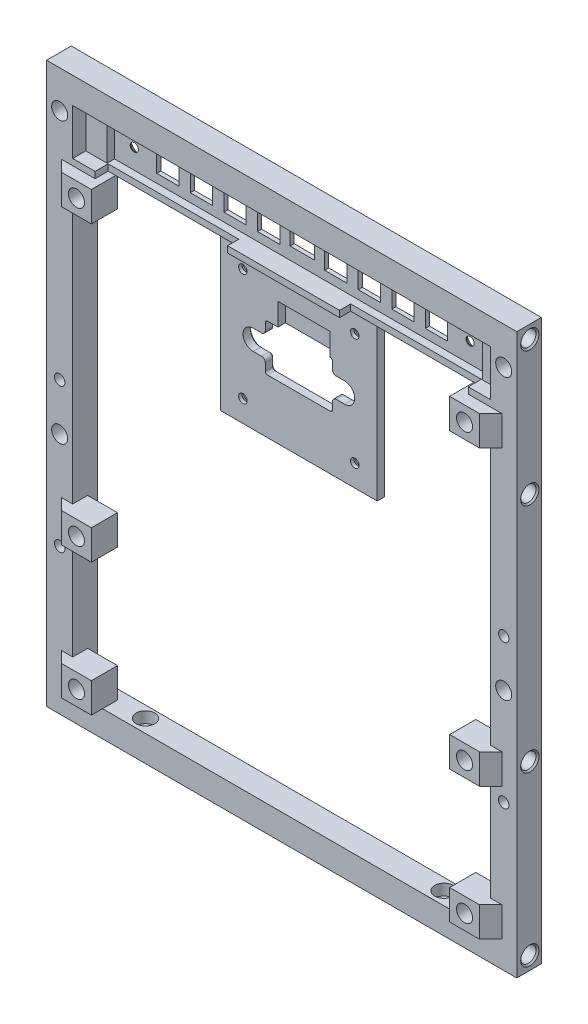
SolidWorks part; units mm, degrees
ref_plane "Front Plane" through (0, 0, 0) normal (0, 0, 1) x (1, 0, 0)
ref_plane "Top Plane" through (0, 0, 0) normal (0, 1, 0) x (1, 0, 0)
ref_plane "Right Plane" through (0, 0, 0) normal (1, 0, 0) x (0, 0, -1)
sketch "Sketch1" plane through (0, 0, 0) normal (0, 0, 1) x (1, 0, 0)
  line L1 (-63, -75) -> (63, -75)
  line L2 (-63, -75) -> (-63, 75)
  line L3 (-63, 75) -> (63, 75)
  line L4 (63, -75) -> (63, 75)
  line L5 (-63, -75) -> (63, 75) construction
  line L6 (-63, 75) -> (63, -75) construction
  line L7 (-56, -68) -> (56, -68)
  line L8 (-56, -68) -> (-56, 68)
  line L9 (-56, 68) -> (56, 68)
  line L10 (56, -68) -> (56, 68)
  line L11 (-56, -68) -> (56, 68) construction
  line L12 (-56, 68) -> (56, -68) construction
  point P0 (0, 0)
  point P6 (0, 0)
  dimension "D1" = 126
  dimension "D2" = 150
  dimension "D3" = 7
  dimension "D4" = 7
extrude "Boss-Extrude1" add sketch "Sketch1" along normal blind 7
sketch "Sketch2" plane through (-63, 0, 0) normal (-1, 0, 0) x (0, 0, 1)
  line L0 (3.5, 71.5) -> (3.5, -71.5) construction
  line L1 (7, 75) -> (0, 75) construction
  circle A0 centre (3.5, -71.5) radius 2.05
  circle A2 centre (3.5, 71.5) radius 2.05
  circle A3 centre (3.5, 35.5) radius 2.05
  circle A4 centre (3.5, -26.5) radius 2.05
  point P2 (3.5, 0)
  point P7 (3.5, 75)
  dimension "D2" = 4.1
  dimension "D3" = 36
  dimension "D4" = 45
  dimension "D1" = 3.5
extrude "Cut-Extrude1" cut sketch "Sketch2" against normal blind 6
mirror "Mirror1" about plane through (0, 0, 0) normal (1, 0, 0) of "Cut-Extrude1"
sketch "Sketch3" plane through (0, -68, 0) normal (0, 1, 0) x (1, 0, 0)
  line L0 (0, 0) -> (0, -7) construction
  line L1 (-56, 0) -> (56, 0) construction
  line L2 (-56, -7) -> (56, -7) construction
  line L3 (40, -3.5) -> (-40, -3.5) construction
  circle A0 centre (40, -3.5) radius 1.35
  circle A1 centre (-40, -3.5) radius 1.35
  point P9 (0, -3.5)
  dimension "D1" = 2.7
  dimension "D2" = 80
extrude "Cut-Extrude2" cut sketch "Sketch3" against normal through all
sketch "Sketch4" plane through (0, -68, 0) normal (0, 1, 0) x (1, 0, 0)
  circle A0 centre (40, -3.5) radius 2.5
  circle A1 centre (-40, -3.5) radius 2.5
  dimension "D1" = 5
extrude "Cut-Extrude3" cut sketch "Sketch4" against normal blind 3
sketch "Sketch5" plane through (0, 0, 0) normal (0, 0, -1) x (-1, 0, 0)
  line L0 (-59.5, -75) -> (-59.5, 75) construction
  line L1 (63, -75) -> (-63, -75) construction
  line L2 (-63, 75) -> (63, 75) construction
  line L3 (-56, 0) -> (-63, 0) construction
  line L4 (-56, -68) -> (-56, 68) construction
  line L5 (-63, -75) -> (-63, 75) construction
  line L6 (0, 75) -> (0, -75) construction
  line L7 (56, -68) -> (-56, -68) construction
  circle A0 centre (-59.5, 2.6) radius 1.4
  circle A1 centre (59.5, 2.6) radius 1.4
  circle A2 centre (-59.5, -36) radius 1.4
  circle A3 centre (59.5, -36) radius 1.4
  point P12 (-59.5, 0)
  point P13 (-59.5, 0)
  dimension "D1" = 2.8
  dimension "D2" = 2.6
  dimension "D3" = 32
extrude "Cut-Extrude4" cut sketch "Sketch5" against normal through all
sketch "Sketch6" plane through (0, 0, 0) normal (0, 0, -1) x (-1, 0, 0)
  circle A0 centre (-59.5, 2.6) radius 2.5
  circle A1 centre (59.5, 2.6) radius 2.5
  circle A2 centre (-59.5, -36) radius 2.5
  circle A3 centre (59.5, -36) radius 2.5
  dimension "D1" = 5
extrude "Cut-Extrude5" cut sketch "Sketch6" against normal blind 3
sketch "Sketch7" plane through (0, 0, 0) normal (0, 0, -1) x (-1, 0, 0)
  line L0 (-56, 68) -> (-63, 68) construction
  line L1 (-63, -75) -> (-63, 75) construction
  line L2 (-59.5, 65) -> (-59.5, -10) construction
  line L3 (-63, 75) -> (63, 75) construction
  circle A0 centre (-59.5, 65) radius 2.15
  circle A1 centre (-59.5, -10) radius 2.15
  point P8 (-59.5, 68)
  dimension "D1" = 4.3
  dimension "D2" = 10
  dimension "D3" = 75
extrude "Cut-Extrude6" cut sketch "Sketch7" against normal through all
mirror "Mirror2" about plane through (0, 0, 0) normal (1, 0, 0) of "Cut-Extrude6"
sketch "Sketch8" plane through (0, 0, 3) normal (0, 0, -1) x (-1, 0, 0)
  line L2 (-60.9, 0.5288) -> (-60.9, 4.6712)
  line L4 (-58.1, 0.5288) -> (-58.1, 4.6712)
  line L5 (-60.9, 0.5288) -> (-58.1, 4.6712) construction
  line L6 (-60.9, 4.6712) -> (-58.1, 0.5288) construction
  line L8 (-60.9, -38.0712) -> (-60.9, -33.9288)
  line L10 (-58.1, -38.0712) -> (-58.1, -33.9288)
  line L11 (-60.9, -38.0712) -> (-58.1, -33.9288) construction
  line L12 (-60.9, -33.9288) -> (-58.1, -38.0712) construction
  circle A0 centre (-59.5, 2.6) radius 2.5 construction
  circle A1 centre (-59.5, -36) radius 2.5 construction
  circle A2 centre (-59.5, -36) radius 2.5 construction
  arc A3 (-58.1, 4.6712) -> (-60.9, 4.6712) centre (-59.5, 2.6) ccw
  arc A4 (-58.1, -33.9288) -> (-60.9, -33.9288) centre (-59.5, -36) ccw
  circle A5 centre (-59.5, 2.6) radius 1.4 construction
  circle A6 centre (-59.5, -36) radius 1.4 construction
  arc A7 (-60.9, -38.0712) -> (-58.1, -38.0712) centre (-59.5, -36) ccw
  arc A8 (-60.9, 0.5288) -> (-58.1, 0.5288) centre (-59.5, 2.6) ccw
  point P0 (-59.5, 2.6)
  point P8 (-59.5, -36)
extrude "Cut-Extrude7" cut sketch "Sketch8" against normal blind 0.2
sketch "Sketch9" plane through (0, 0, 3.2) normal (0, 0, -1) x (-1, 0, 0)
  line L0 (-58.1, 2.6) -> (-58.1, 4.6712) construction
  line L1 (-60.9, 1.2) -> (-58.1, 1.2)
  line L2 (-60.9, 1.2) -> (-60.9, 4)
  line L3 (-60.9, 4) -> (-58.1, 4)
  line L4 (-58.1, 1.2) -> (-58.1, 4)
  line L5 (-60.9, 1.2) -> (-58.1, 4) construction
  line L6 (-60.9, 4) -> (-58.1, 1.2) construction
  line L7 (-58.1, -38.0712) -> (-58.1, -33.9288) construction
  line L8 (-60.9, -37.4) -> (-58.1, -37.4)
  line L9 (-60.9, -37.4) -> (-60.9, -34.6)
  line L10 (-60.9, -34.6) -> (-58.1, -34.6)
  line L11 (-58.1, -37.4) -> (-58.1, -34.6)
  line L12 (-60.9, -37.4) -> (-58.1, -34.6) construction
  line L13 (-60.9, -34.6) -> (-58.1, -37.4) construction
  arc A0 (-58.1, 2.6) -> (-60.9, 2.6) centre (-59.5, 2.6) ccw construction
  point P0 (-59.5, 2.6)
  point P8 (-59.5, -36)
extrude "Cut-Extrude8" cut sketch "Sketch9" against normal blind 0.2
mirror "Mirror3" about plane through (0, 0, 0) normal (1, 0, 0) of "Cut-Extrude8", "Cut-Extrude7"
sketch "Sketch10" plane through (0, 0, 7) normal (0, 0, 1) x (1, 0, 0)
  line L0 (56, -68) -> (56, 68) construction
  line L1 (56, -68) -> (50, -68)
  line L2 (56, -68) -> (56, -62)
  line L3 (56, -62) -> (50, -62)
  line L4 (50, -68) -> (50, -62)
  line L5 (56, -38.5) -> (50, -38.5)
  line L6 (56, -38.5) -> (56, -32.5)
  line L7 (56, -32.5) -> (50, -32.5)
  line L8 (50, -38.5) -> (50, -32.5)
  line L9 (-56, -68) -> (56, -68) construction
  dimension "D1" = 6
  dimension "D2" = 35.5
extrude "Boss-Extrude2" add sketch "Sketch10" against normal offset from surface (5.5 mm away) 1.5 up to face at (-57.35, -10, 0)
sketch "Sketch11" plane through (0, 0, 1.5) normal (0, 0, -1) x (-1, 0, 0)
  line L0 (-56, -38.5) -> (-50, -32.5) construction
  line L2 (-56, -68) -> (-50, -62) construction
  circle A0 centre (-53, -35.5) radius 1.65
  circle A1 centre (-53, -65) radius 1.65
  dimension "D1" = 3.3
extrude "Cut-Extrude9" cut sketch "Sketch11" against normal through all
mirror "Mirror4" about plane through (0, 0, 0) normal (1, 0, 0) of "Cut-Extrude9", "Boss-Extrude2"
sketch "Sketch12" plane through (0, 0, 0) normal (0, 0, -1) x (-1, 0, 0)
  line L0 (56, 68) -> (56, -68) construction
  line L1 (-56, 68) -> (56, 68)
  line L2 (-56, 68) -> (-56, 54)
  line L3 (-56, 54) -> (56, 54)
  line L4 (56, 68) -> (56, 54)
  dimension "D1" = 14
extrude "Boss-Extrude3" add sketch "Sketch12" against normal blind 1.5
sketch "Sketch13" plane through (0, 0, 1.5) normal (0, 0, 1) x (1, 0, 0)
  line L0 (-56, 68) -> (56, 54) construction
  line L2 (-50.3, 55.7) -> (50.3, 55.7)
  line L3 (-50.3, 55.7) -> (-50.3, 66.3)
  line L4 (-50.3, 66.3) -> (50.3, 66.3)
  line L5 (50.3, 55.7) -> (50.3, 66.3)
  line L6 (-50.3, 55.7) -> (50.3, 66.3) construction
  line L7 (-50.3, 66.3) -> (50.3, 55.7) construction
  line L8 (-56, 54) -> (56, 54)
  line L9 (-56, 54) -> (-56, 68)
  line L10 (-56, 68) -> (56, 68)
  line L11 (56, 54) -> (56, 68)
  line L12 (-56, 54) -> (56, 68) construction
  line L13 (-56, 68) -> (56, 54) construction
  point P4 (0, 61)
  point P9 (0, 61)
  dimension "D1" = 100.6
  dimension "D2" = 10.6
extrude "Boss-Extrude4" add sketch "Sketch13" along normal blind 2
sketch "Sketch14" plane through (0, 0, 1.5) normal (0, 0, 1) x (1, 0, 0)
  line L0 (0, 66.3) -> (0, 55.7) construction
  line L1 (50.3, 66.3) -> (-50.3, 66.3) construction
  line L2 (-50.3, 55.7) -> (50.3, 55.7) construction
  line L3 (-50.3, 61) -> (50.3, 61) construction
  line L4 (50.3, 55.7) -> (50.3, 66.3) construction
  line L5 (-33, 64) -> (-39, 64)
  line L6 (-3.25, 59) -> (3.25, 59)
  line L7 (-3.25, 59) -> (-3.25, 63)
  line L8 (-3.25, 63) -> (3.25, 63)
  line L9 (3.25, 59) -> (3.25, 63)
  line L10 (-3.25, 59) -> (3.25, 63) construction
  line L11 (-3.25, 63) -> (3.25, 59) construction
  line L12 (6, 58) -> (12, 58)
  line L13 (6, 58) -> (6, 64)
  line L14 (6, 64) -> (12, 64)
  line L15 (12, 58) -> (12, 64)
  line L16 (6, 58) -> (12, 64) construction
  line L17 (6, 64) -> (12, 58) construction
  line L18 (15, 58) -> (21, 58)
  line L19 (15, 58) -> (15, 64)
  line L20 (15, 64) -> (21, 64)
  line L21 (21, 58) -> (21, 64)
  line L22 (15, 58) -> (21, 64) construction
  line L23 (15, 64) -> (21, 58) construction
  line L24 (24, 58) -> (30, 58)
  line L25 (24, 58) -> (24, 64)
  line L26 (24, 64) -> (30, 64)
  line L27 (30, 58) -> (30, 64)
  line L28 (24, 58) -> (30, 64) construction
  line L29 (24, 64) -> (30, 58) construction
  line L30 (33, 58) -> (39, 58)
  line L31 (33, 58) -> (33, 64)
  line L32 (33, 64) -> (39, 64)
  line L33 (39, 58) -> (39, 64)
  line L34 (33, 58) -> (39, 64) construction
  line L35 (33, 64) -> (39, 58) construction
  line L36 (-39, 58) -> (-39, 64)
  line L37 (-33, 58) -> (-39, 58)
  line L38 (-33, 58) -> (-33, 64)
  line L39 (-24, 64) -> (-30, 64)
  line L40 (-30, 58) -> (-30, 64)
  line L41 (-24, 58) -> (-30, 58)
  line L42 (-24, 58) -> (-24, 64)
  line L43 (-15, 64) -> (-21, 64)
  line L44 (-21, 58) -> (-21, 64)
  line L45 (-15, 58) -> (-21, 58)
  line L46 (-15, 58) -> (-15, 64)
  line L47 (-6, 64) -> (-12, 64)
  line L48 (-12, 58) -> (-12, 64)
  line L49 (-6, 58) -> (-12, 58)
  line L50 (-6, 58) -> (-6, 64)
  circle A0 centre (-45, 61) radius 1.3 construction
  circle A1 centre (45, 61) radius 1.3 construction
  point P6 (0, 61)
  point P11 (0, 61)
  point P16 (9, 61)
  point P21 (18, 61)
  point P26 (27, 61)
  point P31 (36, 61)
  dimension "D10" = 2.6
  dimension "D9" = 45
  dimension "D1" = 6.5
  dimension "D2" = 4
  dimension "D3" = 6
  dimension "D4" = 9
  dimension "D5" = 9
  dimension "D6" = 9
  dimension "D7" = 9
  dimension "D8" = 45
extrude "Cut-Extrude10" cut sketch "Sketch14" against normal through all
sketch "Sketch15" plane through (0, 0, 1.5) normal (0, 0, 1) x (1, 0, 0)
  circle A0 centre (-45, 61) radius 1
  circle A1 centre (45, 61) radius 1
  dimension "D1" = 2
extrude "Boss-Extrude5" add sketch "Sketch15" along normal up to surface (2 mm away) up to face at (0, 61, 3.5)
chamfer "Chamfer1" distance 0.4 angle 45 3 edges at (-56, -7, 0) (56, -7, 0) (0, -68, 0) tangent propagation no
chamfer "Chamfer2" distance 0.4 angle 45 4 edges at (0, 75, 0) (-63, 0, 0) (0, -75, 0) (63, 0, 0)
chamfer "Chamfer3" distance 0.4 angle 45 36 edges at (-36, 58, 0) (-39, 61, 0) (-36, 64, 0) (-33, 61, 0) (-27, 58, 0) (-30, 61, 0) (-27, 64, 0) (-24, 61, 0) (-18, 58, 0) (-21, 61, 0) (-18, 64, 0) (-15, 61, 0) (-9, 58, 0) (-12, 61, 0) (-9, 64, 0) (-6, 61, 0) (0, 59, 0) (-3.25, 61, 0) (0, 63, 0) (3.25, 61, 0) (9, 58, 0) (6, 61, 0) (9, 64, 0) (12, 61, 0) (18, 58, 0) (15, 61, 0) (18, 64, 0) (21, 61, 0) (36, 58, 0) (33, 61, 0) (36, 64, 0) (39, 61, 0) (27, 58, 0) (24, 61, 0) (27, 64, 0) (30, 61, 0)
sketch "Sketch16" plane through (0, 0, 7) normal (0, 0, 1) x (1, 0, 0)
  line L0 (-50, 54) -> (-50, 55.7)
  line L1 (-56, -32.5) -> (-50, -32.5)
  line L2 (-56, -32.5) -> (-56, -26.5)
  line L3 (-56, -26.5) -> (-50, -26.5)
  line L4 (-50, -32.5) -> (-50, -26.5)
  line L5 (56, -32.5) -> (50, -32.5)
  line L6 (56, -32.5) -> (56, -26.5)
  line L7 (56, -26.5) -> (50, -26.5)
  line L8 (50, -32.5) -> (50, -26.5)
  line L9 (56, 54) -> (50, 54) construction
  line L10 (56, 54) -> (56, 48)
  line L11 (56, 48) -> (50, 48)
  line L12 (50, 54) -> (50, 48)
  line L13 (-56, 54) -> (-50, 54) construction
  line L14 (-56, 54) -> (-56, 48)
  line L15 (-56, 48) -> (-50, 48)
  line L16 (-50, 54) -> (-50, 48)
  line L17 (-50.3, 55.7) -> (50.3, 55.7) construction
  line L18 (-50, 55.7) -> (-56, 55.7)
  line L19 (-56, 68) -> (-56, 54) construction
  line L20 (-56, 55.7) -> (-56, 54)
  line L21 (50, 54) -> (50, 55.7)
  line L22 (50, 55.7) -> (56, 55.7)
  line L23 (56, 54) -> (56, 68) construction
  line L24 (56, 55.7) -> (56, 54)
  dimension "D1" = 6
extrude "Boss-Extrude7" add sketch "Sketch16" against normal offset from surface (5.5 mm away) 1.5 up to face at (-36, 61, 0)
sketch "Sketch17" plane through (0, 0, 1.5) normal (0, 0, -1) x (-1, 0, 0)
  line L0 (-50, 48) -> (50, -26.5) construction
  line L1 (-50, -26.5) -> (-50, -38.5) construction
  line L2 (-53, -29.5) -> (53, -29.5) construction
  line L3 (-53, -29.5) -> (-53, 51) construction
  line L4 (-53, 51) -> (53, 51) construction
  line L5 (53, -29.5) -> (53, 51) construction
  line L6 (-53, -29.5) -> (53, 51) construction
  line L7 (-53, 51) -> (53, -29.5) construction
  line L8 (50, -26.5) -> (56, -26.5) construction
  circle A0 centre (-53, -29.5) radius 1.65
  circle A1 centre (53, -29.5) radius 1.65
  circle A2 centre (53, 51) radius 1.65
  circle A3 centre (-53, 51) radius 1.65
  point P4 (0, 10.75)
  dimension "D3" = 3.3
  dimension "D1" = 3
  dimension "D2" = 3
extrude "Cut-Extrude11" cut sketch "Sketch17" against normal through all
sketch "Sketch18" plane through (0, 0, 1.5) normal (0, 0, 1) x (1, 0, 0)
  circle A0 centre (-45, 61) radius 1.1
  circle A1 centre (45, 61) radius 1.1
  dimension "D1" = 2.2
extrude "Cut-Extrude12" cut sketch "Sketch18" against normal through all both and the other way through all
chamfer "Chamfer4" distance 1.3 angle 45 2 edges at (-43.9, 61, 0) (46.1, 61, 0)
sketch "Sketch19" plane through (0, 0, 1.5) normal (0, 0, -1) x (-1, 0, 0)
  line L1 (-56, -68) -> (56, -68)
  line L2 (-56, -68) -> (-56, 54)
  line L3 (-56, 54) -> (56, 54)
  line L4 (56, -68) -> (56, 54)
extrude "Cut-Extrude13" cut sketch "Sketch19" against normal through all
ref_plane "Plane1" through (0, 0, 3) normal (0, 0, 1) x (1, 0, 0)
sketch "Sketch20" plane through (0, 0, 3) normal (0, 0, 1) x (1, 0, 0)
  line L0 (56, 54) -> (56, -68) construction
  line L1 (56, -68) -> (48, -68)
  line L2 (56, -68) -> (56, -60)
  line L3 (56, -60) -> (48, -60)
  line L4 (48, -68) -> (48, -60)
  line L5 (56, 54) -> (48, 54)
  line L6 (56, 54) -> (56, 46)
  line L7 (56, 46) -> (48, 46)
  line L8 (48, 54) -> (48, 46)
  line L9 (56, -24.5) -> (48, -24.5)
  line L10 (56, -24.5) -> (56, -32.5)
  line L11 (56, -32.5) -> (48, -32.5)
  line L12 (48, -24.5) -> (48, -32.5)
  dimension "D1" = 8
  dimension "D2" = 27.5
extrude "Boss-Extrude8" add sketch "Sketch20" along normal blind 7
sketch "Sketch21" plane through (0, 0, 3) normal (0, 0, -1) x (-1, 0, 0)
  line L0 (-48, 54) -> (-56, 46) construction
  line L1 (-56, -60) -> (-48, -68) construction
  line L2 (-56, -24.5) -> (-48, -32.5) construction
  circle A0 centre (-52, 50) radius 2.15
  circle A1 centre (-52, -64) radius 2.15
  circle A2 centre (-52, -28.5) radius 2.15
  dimension "D1" = 4.3
extrude "Cut-Extrude14" cut sketch "Sketch21" against normal through all
mirror "Mirror5" about plane through (0, 0, 0) normal (1, 0, 0) of "Cut-Extrude14", "Boss-Extrude8"
chamfer "Chamfer5" distance 3 angle 45 6 edges at (-56, -64, 7) (56, -64, 7) (56, 50, 7) (-56, 50, 7) (-56, -28.5, 7) (56, -28.5, 7)
sketch "Sketch23" plane through (0, 0, 0) normal (0, 0, -1) x (-1, 0, 0)
  line L0 (-56.4, 54) -> (56.4, 54) construction
  line L1 (-15, 54) -> (15, 54)
  line L2 (-15, 54) -> (-15, 29)
  line L3 (-15, 29) -> (15, 29)
  line L4 (15, 54) -> (15, 29)
  point P6 (0, 29)
  dimension "D1" = 25
  dimension "D2" = 30
extrude "Boss-Extrude10" add sketch "Sketch23" against normal up to surface (3.5 mm away) up to face at (0, 54.5667, 3.5)
sketch "Sketch24" plane through (0, 0, 3.5) normal (0, 0, 1) x (1, 0, 0)
  line L0 (15, 29) -> (-15, 29) construction
  line L1 (-12.7, 29) -> (12.7, 29)
  line L2 (-12.7, 29) -> (-12.7, 54)
  line L3 (-12.7, 54) -> (12.7, 54)
  line L4 (12.7, 29) -> (12.7, 54)
  line L5 (-48, 54) -> (-15, 54) construction
  point P6 (0, 29)
  dimension "D1" = 25.4
extrude "Cut-Extrude15" cut sketch "Sketch24" against normal offset from surface (2.5 mm away) 1 up to face at (-47.4, 61, 0)
sketch "Sketch26" plane through (0, 0, 1) normal (0, 0, 1) x (1, 0, 0)
  line L0 (12.7, 54) -> (-12.7, 54) construction
  line L1 (-12.5, 53.4) -> (12.5, 53.4) construction
  line L2 (-12.5, 53.4) -> (-12.5, 29.538) construction
  line L3 (-12.5, 29.538) -> (12.5, 29.538) construction
  line L4 (12.5, 53.4) -> (12.5, 29.538) construction
  line L5 (0, 53.4) -> (0, 29.538) construction
  line L6 (-10.5, 51.4) -> (10.5, 51.4) construction
  line L7 (-10.5, 51.4) -> (-10.5, 38.9) construction
  line L8 (-10.5, 38.9) -> (10.5, 38.9) construction
  line L9 (10.5, 51.4) -> (10.5, 38.9) construction
  line L10 (12.7, 54) -> (-12.7, 54) construction
  line L11 (-5.4, 33.6) -> (5.4, 33.6) construction
  line L12 (-5.4, 33.6) -> (-5.4, 44.4) construction
  line L13 (-5.4, 44.4) -> (5.4, 44.4) construction
  line L14 (5.4, 33.6) -> (5.4, 44.4) construction
  line L15 (-5.4, 33.6) -> (5.4, 44.4) construction
  line L16 (-5.4, 44.4) -> (5.4, 33.6) construction
  circle A0 centre (-10.5, 51.4) radius 1.1 construction
  circle A1 centre (10.5, 51.4) radius 1.1 construction
  circle A2 centre (10.5, 38.9) radius 1.1 construction
  circle A3 centre (-10.5, 38.9) radius 1.1 construction
  point P4 (0, 53.4)
  point P7 (0, 54)
  point P12 (0, 51.4)
  point P19 (0, 39)
  dimension "D3" = 2.2
  dimension "D1" = 25
  dimension "D2" = 23.862
  dimension "D4" = 2
  dimension "D5" = 14.5
  dimension "D6" = 10.8
  dimension "D7" = 10.8
  dimension "D8" = 14.4
  dimension "D9" = 0.6
  dimension "D10" = 2
sketch "Sketch27" plane through (0, 0, 1) normal (0, 0, 1) x (1, 0, 0)
  line L0 (-12.7, 54) -> (-12.7, 29) construction
  line L1 (-12.7, 54) -> (-8.5, 54)
  line L2 (-12.7, 54) -> (-12.7, 49.4)
  line L3 (-12.7, 49.4) -> (-8.5, 49.4)
  line L4 (-8.5, 54) -> (-8.5, 49.4)
  line L5 (-12.7, 36.9) -> (-8.5, 36.9)
  line L6 (-12.7, 36.9) -> (-12.7, 40.9)
  line L7 (-12.7, 40.9) -> (-8.5, 40.9)
  line L8 (-8.5, 36.9) -> (-8.5, 40.9)
  line L9 (0, 54) -> (0, 29) construction
  line L10 (12.7, 54) -> (-12.7, 54) construction
  line L11 (-12.7, 29) -> (12.7, 29) construction
  line L12 (8.5, 36.9) -> (8.5, 40.9)
  line L13 (12.7, 40.9) -> (8.5, 40.9)
  line L14 (12.7, 36.9) -> (12.7, 40.9)
  line L15 (12.7, 36.9) -> (8.5, 36.9)
  line L16 (8.5, 54) -> (8.5, 49.4)
  line L17 (12.7, 49.4) -> (8.5, 49.4)
  line L18 (12.7, 54) -> (12.7, 49.4)
  line L19 (12.7, 54) -> (8.5, 54)
  dimension "D1" = 2
  dimension "D2" = 2
  dimension "D3" = 2
  dimension "D4" = 2
  dimension "D5" = 2
extrude "Boss-Extrude11" add sketch "Sketch27" along normal blind 3
sketch "Sketch28" plane through (0, 0, 1) normal (0, 0, 1) x (1, 0, 0)
  line L0 (-5.4, 44.4) -> (5.4, 44.4) construction
  line L1 (-6, 33) -> (6, 33)
  line L2 (-6, 33) -> (-6, 45)
  line L3 (-6, 45) -> (6, 45)
  line L4 (6, 33) -> (6, 45)
  line L5 (-6, 33) -> (6, 45) construction
  line L6 (-6, 45) -> (6, 33) construction
  line L7 (5.4, 33.6) -> (5.4, 44.4) construction
  point P0 (0, 39)
  dimension "D1" = 0.6
  dimension "D2" = 0.6
extrude "Cut-Extrude16" cut sketch "Sketch28" against normal through all
sketch "Sketch29" plane through (0, 0, 4) normal (0, 0, 1) x (1, 0, 0)
  circle A0 centre (-10.5, 38.9) radius 1.1
  circle A1 centre (-10.5, 51.4) radius 1.1
  circle A2 centre (10.5, 51.4) radius 1.1
  circle A3 centre (10.5, 38.9) radius 1.1
  dimension "D1" = 2.2
extrude "Cut-Extrude17" cut sketch "Sketch29" against normal through all
chamfer "Chamfer6" distance 1.3 angle 45 4 edges at (11.6, 38.9, 0) (-9.4, 38.9, 0) (-9.4, 51.4, 0) (11.6, 51.4, 0)
chamfer "Chamfer7" distance 0.4 angle 45 4 edges at (0, 33, 0) (-6, 39, 0) (0, 45, 0) (6, 39, 0)
chamfer "Chamfer8" distance 0.4 angle 45 2 edges at (-35.7, 54, 0) (35.7, 54, 0)
sketch "Sketch30" plane through (0, 0, 3.5) normal (0, 0, 1) x (1, 0, 0)
  line L0 (-12.7, 29) -> (-12.7, 54)
  line L1 (-12.7, 54) -> (12.7, 54)
  line L2 (12.7, 54) -> (12.7, 29)
  line L3 (12.7, 29) -> (15, 29)
  line L4 (15, 29) -> (15, 55.7)
  line L5 (-50.3, 55.7) -> (50.3, 55.7) construction
  line L6 (15, 55.7) -> (-15, 55.7)
  line L7 (-15, 55.7) -> (-15, 29)
  line L8 (-12.7, 29) -> (-15, 29)
extrude "Boss-Extrude12" add sketch "Sketch30" along normal blind 3
chamfer "Chamfer9" distance 0.4 angle 45 18 edges at (-49.85, -64, 3) (-57.35, -10, 0) (-49.85, -28.5, 3) (-49.85, 50, 3) (-57.35, 65, 0) (49.85, -64, 3) (49.85, -28.5, 3) (49.85, 50, 3) (57.35, -10, 0) (57.35, 65, 0) (63, 71.5, 5.55) (63, 35.5, 5.55) (63, -26.5, 5.55) (63, -71.5, 5.55) (-63, -71.5, 5.55) (-63, -26.5, 5.55) (-63, 35.5, 5.55) (-63, 71.5, 5.55)
sketch "Sketch31" plane through (0, 0, 1) normal (0, 0, 1) x (1, 0, 0)
  line L1 (-15, 29) -> (15, 29)
  line L2 (-15, 29) -> (-15, 54)
  line L3 (-15, 54) -> (15, 54)
  line L4 (15, 29) -> (15, 54)
extrude "Cut-Extrude18" cut sketch "Sketch31" against normal through all both and the other way through all
sketch "Sketch32" plane through (0, 0, 0) normal (0, 0, -1) x (-1, 0, 0)
  line L0 (-56.4, 54.4) -> (-15, 54.4) construction
  line L1 (-21, 54.4) -> (21, 54.4)
  line L2 (-21, 54.4) -> (-21, 12.4)
  line L3 (-21, 12.4) -> (21, 12.4)
  line L4 (21, 54.4) -> (21, 12.4)
  point P6 (0, 12.4)
  dimension "D1" = 42
extrude "Boss-Extrude13" add sketch "Sketch32" against normal blind 2.4
sketch "Sketch33" plane through (0, 0, 2.4) normal (0, 0, 1) x (1, 0, 0)
  line L0 (-21, 12.4) -> (21, 54) construction
  line L1 (-12.25, 33.2) -> (12.25, 33.2) construction
  line L2 (-19, 14.2) -> (19, 14.2) construction
  line L3 (-19, 14.2) -> (-19, 52.2) construction
  line L4 (-19, 52.2) -> (19, 52.2) construction
  line L5 (19, 14.2) -> (19, 52.2) construction
  line L6 (-19, 14.2) -> (19, 52.2) construction
  line L7 (-19, 52.2) -> (19, 14.2) construction
  line L8 (-15, 18.2) -> (15, 18.2) construction
  line L9 (-15, 18.2) -> (-15, 48.2) construction
  line L10 (-15, 48.2) -> (15, 48.2) construction
  line L11 (15, 18.2) -> (15, 48.2) construction
  line L12 (-15, 18.2) -> (15, 48.2) construction
  line L13 (-15, 48.2) -> (15, 18.2) construction
  line L14 (-8.4, 26.95) -> (8.4, 26.95)
  line L15 (-9, 27.55) -> (-9, 29.5)
  line L16 (-8.4, 39.45) -> (8.4, 39.45)
  line L17 (9, 27.55) -> (9, 29.5)
  line L18 (-9, 26.95) -> (9, 39.45) construction
  line L19 (-9, 39.45) -> (9, 26.95) construction
  line L20 (12.25, 35.9) -> (10, 35.9)
  line L21 (12.25, 30.5) -> (10, 30.5)
  line L22 (9, 36.9) -> (9, 38.85)
  line L23 (-12.25, 35.9) -> (-10, 35.9)
  line L24 (-12.25, 30.5) -> (-10, 30.5)
  line L25 (-9, 36.9) -> (-9, 38.85)
  circle A0 centre (-15, 48.2) radius 1.15
  circle A1 centre (15, 48.2) radius 1.15
  circle A2 centre (15, 18.2) radius 1.15
  circle A3 centre (-15, 18.2) radius 1.15
  arc A4 (12.25, 30.5) -> (12.25, 35.9) centre (12.25, 33.2) ccw
  arc A5 (-12.25, 35.9) -> (-12.25, 30.5) centre (-12.25, 33.2) ccw
  arc A6 (9, 29.5) -> (10, 30.5) centre (10, 29.5) cw
  arc A7 (10, 35.9) -> (9, 36.9) centre (10, 36.9) cw
  arc A8 (-9, 29.5) -> (-10, 30.5) centre (-10, 29.5) ccw
  arc A9 (-9, 36.9) -> (-10, 35.9) centre (-10, 36.9) cw
  arc A10 (-9, 27.55) -> (-8.4, 26.95) centre (-8.4, 27.55) ccw
  arc A11 (8.4, 26.95) -> (9, 27.55) centre (8.4, 27.55) ccw
  arc A12 (8.4, 39.45) -> (9, 38.85) centre (8.4, 38.85) cw
  arc A13 (-9, 38.85) -> (-8.4, 39.45) centre (-8.4, 38.85) cw
  point P4 (0, 33.2)
  point P9 (0, 33.2)
  point P18 (0, 33.2)
  point P26 (0, 33.2)
  point P36 (9, 30.5)
  point P39 (9, 35.9)
  point P44 (-9, 35.9)
  dimension "D3" = 2.3
  dimension "D7" = 5.4
  dimension "D8" = 1
  dimension "D9" = 0.6
  dimension "D1" = 38
  dimension "D2" = 30
  dimension "D4" = 12.5
  dimension "D5" = 18
  dimension "D6" = 24.5
extrude "Cut-Extrude19" cut sketch "Sketch33" against normal through all
sketch "Sketch34" plane through (0, 0, 2.4) normal (0, 0, 1) x (1, 0, 0)
  line L1 (8.4, 39.45) -> (-5.6, 39.45)
  line L2 (8.4, 39.45) -> (8.4, 45.45)
  line L3 (8.4, 45.45) -> (-5.6, 45.45)
  line L4 (-5.6, 39.45) -> (-5.6, 45.45)
  dimension "D1" = 14
  dimension "D2" = 6
extrude "Cut-Extrude20" cut sketch "Sketch34" against normal blind 2
chamfer "Chamfer10" distance 0.4 angle 45 20 edges at (0, 26.95, 0) (8.8243, 27.1257, 0) (-8.8243, 27.1257, 0) (9, 28.525, 0) (-9, 28.525, 0) (9.2929, 30.2071, 0) (-9.2929, 30.2071, 0) (11.125, 30.5, 0) (-11.125, 30.5, 0) (14.95, 33.2, 0) (-14.95, 33.2, 0) (11.125, 35.9, 0) (-11.125, 35.9, 0) (9.2929, 36.1929, 0) (-9.2929, 36.1929, 0) (9, 37.875, 0) (-9, 37.875, 0) (8.8243, 39.2743, 0) (-8.8243, 39.2743, 0) (0, 39.45, 0)
chamfer "Chamfer11" distance 1.5 angle 45 4 edges at (-13.85, 18.2, 0) (16.15, 18.2, 0) (-13.85, 48.2, 0) (16.15, 48.2, 0)
chamfer "Chamfer12" distance 0.4 angle 45 3 edges at (-21, 33.4, 0) (0, 12.4, 0) (21, 33.4, 0)
